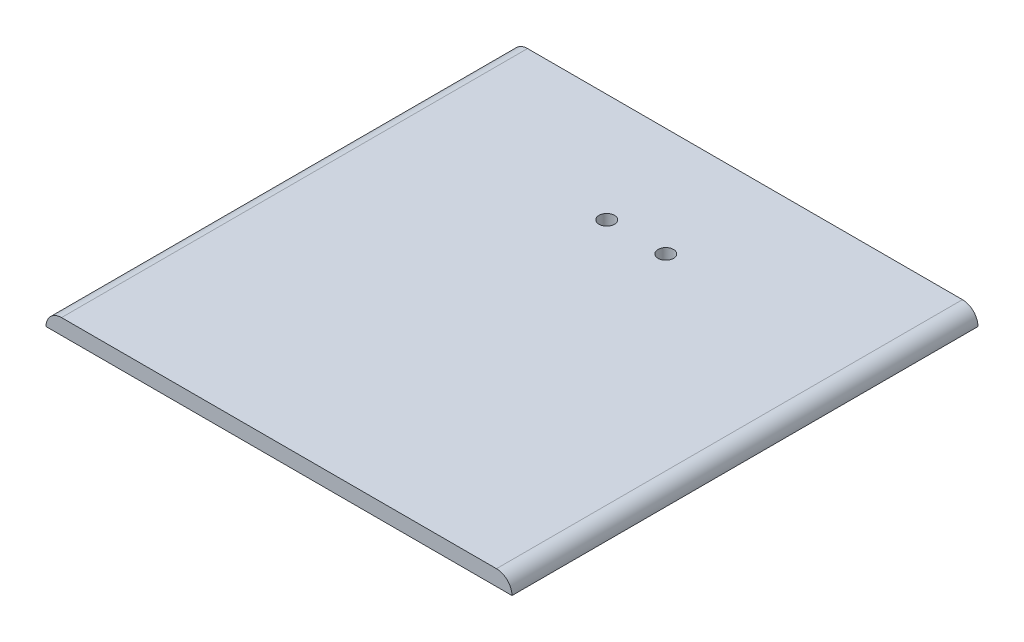
SolidWorks part; units mm, degrees
ref_plane "Front Plane" through (0, 0, 0) normal (0, 0, 1) x (1, 0, 0)
ref_plane "Top Plane" through (0, 0, 0) normal (0, 1, 0) x (1, 0, 0)
ref_plane "Right Plane" through (0, 0, 0) normal (1, 0, 0) x (0, 0, -1)
sketch "Sketch1" plane through (0, 0, 0) normal (0, 1, 0) x (1, 0, 0)
  line L1 (-150, 150) -> (150, 150)
  line L2 (-150, 150) -> (-150, -150)
  line L3 (-150, -150) -> (150, -150)
  line L4 (150, 150) -> (150, -150)
  line L5 (-150, 150) -> (150, -150) construction
  line L6 (-150, -150) -> (150, 150) construction
  point P0 (0, 0)
  dimension "D1" = 300
  dimension "D2" = 300
extrude "Boss-Extrude1" add sketch "Sketch1" along normal blind 10
sketch "Sketch2" plane through (0, 10, 0) normal (0, 1, 0) x (1, 0, 0)
  line L0 (150, 150) -> (-150, 150) construction
  circle A0 centre (-19, 80) radius 5
  circle A1 centre (19, 80) radius 5
  point P5 (0, 0)
  dimension "D4" = 10
  dimension "D5" = 10
  dimension "D1" = 38
  dimension "D2" = 19
  dimension "D3" = 70
extrude "Cut-Extrude1" cut sketch "Sketch2" against normal blind 10
fillet "Fillet2" radius 10 1 edges at (-150, 10, 0)
fillet "Fillet3" radius 10 1 edges at (150, 10, 0)
